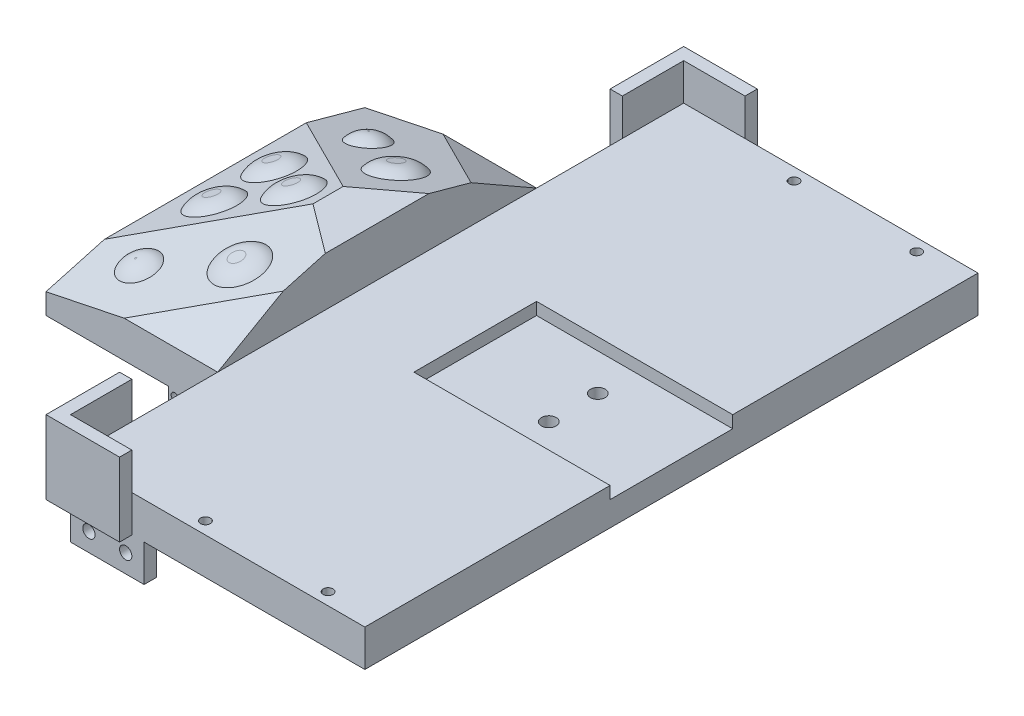
SolidWorks part; units mm, degrees
ref_plane "Ebene vorne" through (0, 0, 0) normal (0, 0, 1) x (1, 0, 0)
ref_plane "Ebene oben" through (0, 0, 0) normal (0, 1, 0) x (1, 0, 0)
ref_plane "Ebene rechts" through (0, 0, 0) normal (1, 0, 0) x (0, 0, -1)
sketch "Skizze1" plane through (0, 0, 0) normal (0, 1, 0) x (1, 0, 0)
  line L5 (-175, -125) -> (175, 125) construction
  line L6 (-175, 125) -> (175, -125) construction
  line L11 (-105, 125) -> (145, 125)
  line L12 (-105, -125) -> (-105, -65)
  line L13 (-105, 125) -> (-105, 65)
  line L14 (-105, -65) -> (-175, -65)
  line L15 (-105, 65) -> (-175, 65)
  line L17 (-105, -125) -> (145, -125)
  line L19 (185, 20) -> (145, 125)
  line L21 (175, 0) -> (175, 20)
  line L22 (175, 20) -> (185, 20)
  line L23 (185, 0) -> (185, 20)
  line L25 (185, 0) -> (185, -20)
  line L26 (185, -20) -> (175, -20)
  line L27 (175, 0) -> (175, -20)
  line L28 (185, -20) -> (145, -125)
  line L29 (-175, 65) -> (-175, -65)
  point P0 (0, 0)
  dimension "D1" = 350
  dimension "D2" = 250
  dimension "D3" = 60
  dimension "D4" = 250
  dimension "D5" = 40
  dimension "D6" = 130
  dimension "D7" = 70
  dimension "D8" = 20
  dimension "D9" = 10
extrude "Aufsatz-Linear austragen1" add sketch "Skizze1" along normal blind 15 contours L15 L29 L14 L12 L17 L28 L26 L27 L21 L22 L19 L11 L13 | L21 L27 L26 L25 L23 L22 region at (10.8182, 0, 0) region at (180, 0, 0)
sketch "Skizze2" plane through (0, 15, 0) normal (0, 1, 0) x (1, 0, 0)
  line L0 (-175, 65) -> (-175, -65) construction
  line L9 (-175, 62) -> (-110, 62)
  line L10 (-175, 62) -> (-175, 42)
  line L11 (-175, 42) -> (-110, 42)
  line L12 (-110, 62) -> (-110, 42)
  line L13 (-105, 65) -> (-175, 65) construction
  line L14 (-175, -42) -> (-110, -42)
  line L15 (-175, -42) -> (-175, -62)
  line L16 (-175, -62) -> (-110, -62)
  line L17 (-110, -42) -> (-110, -62)
  line L18 (-105, -65) -> (-175, -65) construction
  line L19 (-105, 125) -> (145, 125) construction
  line L24 (-125, -62) -> (-120, -62)
  line L25 (-125, -62) -> (-125, -65)
  line L26 (-125, -65) -> (-120, -65)
  line L27 (-120, -62) -> (-120, -65)
  line L28 (-125, -42) -> (-120, -42)
  line L29 (-125, -42) -> (-125, -38)
  line L30 (-125, -38) -> (-120, -38)
  line L31 (-120, -42) -> (-120, -38)
  line L32 (-125, 42) -> (-120, 42)
  line L33 (-125, 42) -> (-125, 38)
  line L34 (-125, 38) -> (-120, 38)
  line L35 (-120, 42) -> (-120, 38)
  line L36 (-125, 65) -> (-120, 65)
  line L37 (-125, 65) -> (-125, 62)
  line L38 (-125, 62) -> (-120, 62)
  line L39 (-120, 65) -> (-120, 62)
  line L40 (-105, -125) -> (145, -125)
  line L41 (-105, -125) -> (-105, 125)
  line L42 (-105, 125) -> (145, 125)
  line L43 (145, -125) -> (145, 125)
  line L46 (145, -125) -> (195, -125)
  line L47 (145, -125) -> (145, 125)
  line L48 (145, 125) -> (195, 125)
  line L49 (195, -125) -> (195, 125)
  line M8 (-105, 65) -> (-175, 65)
  dimension "D1" = 65
  dimension "D2" = 65
  dimension "D3" = 20
  dimension "D4" = 20
  dimension "D5" = 3
  dimension "D6" = 3
  dimension "D7" = 5
  dimension "D8" = 50
  dimension "D9" = 5
  dimension "D10" = 50
  dimension "D11" = 5
  dimension "D12" = 50
  dimension "D13" = 5
  dimension "D14" = 50
  dimension "D15" = 4
  dimension "D16" = 4
  dimension "D17" = 250
  dimension "D18" = 50
extrude "Aufsatz-Linear austragen2" add sketch "Skizze2" against normal blind 37 contours L14 L31 L30 L29 | L35 L11 L33 L34 | L39 L37 L9 M8 | L26 L27 L24 L25 region at (-122.5, 15, -63.5) region at (-122.5, 15, -40) region at (-122.5, 15, 40)
sketch "Skizze3" plane through (0, 15, 0) normal (0, 1, 0) x (1, 0, 0)
  line L0 (-105, 125) -> (145, 125) construction
  line L1 (-105, -125) -> (145, -125)
  line L2 (-105, -125) -> (-105, 125)
  line L3 (-105, 125) -> (145, 125)
  line L4 (145, -125) -> (145, 125)
  line L6 (145, -125) -> (195, -125)
  line L7 (145, -125) -> (145, 125)
  line L8 (145, 125) -> (195, 125)
  line L9 (195, -125) -> (195, 125)
  line M6 (145, -125) -> (185, -20)
  line M7 (185, -20) -> (185, 20)
  line M8 (185, 20) -> (145, 125)
  dimension "D1" = 250
  dimension "D2" = 50
extrude "Aufsatz-Linear austragen3" add sketch "Skizze3" against normal blind 15 contours L6 L9 L8 M8 M7 M6 region at (167.3825, 15, 73.4076)
sketch "Skizze4" plane through (0, 15, 0) normal (0, 1, 0) x (1, 0, 0)
  line L9 (195, -125) -> (200, -125)
  line L10 (195, -125) -> (195, 125)
  line L11 (195, 125) -> (200, 125)
  line L12 (200, -125) -> (200, 125)
  dimension "D3" = 250
  dimension "D4" = 5
extrude "Aufsatz-Linear austragen4" add sketch "Skizze4" against normal blind 15
sketch "Skizze5" plane through (0, 15, 0) normal (0, 1, 0) x (1, 0, 0)
  line L1 (-105, 125) -> (-75, 125)
  line L2 (-105, 125) -> (-105, 120)
  line L3 (-105, 120) -> (-75, 120)
  line L4 (-75, 125) -> (-75, 120)
  line L5 (-105, -125) -> (-75, -125)
  line L6 (-105, -125) -> (-105, -120)
  line L7 (-105, -120) -> (-75, -120)
  line L8 (-75, -125) -> (-75, -120)
  dimension "D1" = 30
  dimension "D2" = 30
  dimension "D3" = 5
  dimension "D4" = 5
extrude "Aufsatz-Linear austragen5" add sketch "Skizze5" against normal blind 30
sketch "Skizze6" plane through (0, 15, 0) normal (0, 1, 0) x (1, 0, 0)
  line L0 (-105, -125) -> (200, -125) construction
  line L1 (-110, -130) -> (-70.4119, -130)
  line L2 (-110, -130) -> (-110, -86.8064)
  line L3 (-110, -86.8064) -> (-70.4119, -86.8064)
  line L4 (-70.4119, -130) -> (-70.4119, -86.8064)
  line L5 (-110, 130) -> (-61.5934, 130)
  line L6 (-110, 130) -> (-110, 88.8696)
  line L7 (-110, 88.8696) -> (-61.5934, 88.8696)
  line L8 (-61.5934, 130) -> (-61.5934, 88.8696)
  line L9 (-105, -125) -> (-105, -65) construction
  line L10 (-105, 125) -> (-105, 65) construction
  line L11 (-105, 125) -> (200, 125) construction
  line L12 (-68.8744, -125) -> (-105, -125)
  line L13 (-105, -125) -> (-105, -86.8064)
  line L14 (-105, 84.0053) -> (-105, 125)
  line L15 (-105, 125) -> (-61.5934, 125)
  line M6 (-105, -65) -> (-105, -125)
  line M7 (-105, -125) -> (200, -125)
  line M9 (200, 125) -> (-105, 125)
  line M10 (-105, 125) -> (-105, 65)
  dimension "D1" = 5
  dimension "D2" = 5
  dimension "D3" = 5
  dimension "D4" = 5
extrude "Aufsatz-Linear austragen6" add sketch "Skizze6" along normal blind 15 separate body contours L8 L5 L6 L7 M10 M9 | L1 L4 L3 L2 M7 M6 region at (-109.4141, 15, 108.4032) region at (-85.7967, 15, -129.3648)
sketch "Skizze7" plane through (0, 0, 0) normal (0, -1, 0) x (1, 0, 0)
  line L7 (-110, -130) -> (-110, -88.8696)
  line L8 (-110, -88.8696) -> (-105, -88.8696)
  line L9 (-105, -130) -> (-105, -88.8696)
  line L10 (-110, 130) -> (-105, 130)
  line L11 (-110, 130) -> (-110, 86.8064)
  line L12 (-110, 86.8064) -> (-105, 86.8064)
  line L13 (-105, 130) -> (-105, 86.8064)
  line L14 (-110, 130) -> (-70.4119, 130)
  line L15 (-110, 130) -> (-110, 125)
  line L16 (-110, 125) -> (-70.4119, 125)
  line L17 (-70.4119, 130) -> (-70.4119, 125)
  line L18 (-110, -130) -> (-61.5934, -130)
  line L19 (-110, -130) -> (-110, -125)
  line L20 (-110, -125) -> (-61.5934, -125)
  line L21 (-61.5934, -130) -> (-61.5934, -125)
  line M7 (-105, 120) -> (-105, 65)
  line M19 (-105, -65) -> (-105, -120)
  line M22 (-75, -125) -> (200, -125)
  line M24 (200, 125) -> (-75, 125)
extrude "Aufsatz-Linear austragen7" add sketch "Skizze7" against normal blind 15 contours L7 L20 L9 L8 M19 | L20 L7 L18 L9 | L18 L21 L20 L9 M22 | L16 L11 L12 L13 M7 | L11 L16 L13 L10 | L17 L14 L13 L16 M24 region at (-107.5, 0, -127.5) region at (-107.5, 0, -106.9348) region at (-83.2967, 0, -127.5) region at (-107.5, 0, 127.5) region at (-87.7059, 0, 127.5) region at (-107.5, 0, 105.9032)
sketch "Skizze8" plane through (0, 15, 0) normal (0, 1, 0) x (1, 0, 0)
  line L0 (-61.5934, 125) -> (200, 125) construction
  line L1 (-105, -125) -> (145, -125)
  line L2 (-105, -125) -> (-105, 125)
  line L3 (-105, 125) -> (145, 125)
  line L4 (145, -125) -> (145, 125)
  line L6 (150, -130) -> (109.2888, -130)
  line L7 (150, -130) -> (150, -94.2536)
  line L8 (150, -94.2536) -> (109.2888, -94.2536)
  line L9 (109.2888, -130) -> (109.2888, -94.2536)
  line L10 (150, 130) -> (118.9946, 130)
  line L11 (150, 130) -> (150, 95.9912)
  line L12 (150, 95.9912) -> (118.9946, 95.9912)
  line L13 (118.9946, 130) -> (118.9946, 95.9912)
  line M9 (-70.4119, -125) -> (200, -125)
  line M11 (200, 125) -> (-61.5934, 125)
  dimension "D1" = 250
  dimension "D2" = 5
  dimension "D3" = 5
  dimension "D4" = 5
  dimension "D5" = 5
extrude "Aufsatz-Linear austragen8" add sketch "Skizze8" along normal blind 15 and the other way blind 15 contours L7 L8 L4 M9 | L9 L6 L7 L1 M9 | L12 L11 L4 M11 | L10 L13 L11 M11 region at (129.6444, 15, 127.5) region at (147.5, 15, 109.6268) region at (134.4973, 15, -127.5) region at (147.5, 15, -110.4956)
sketch "Skizze9" plane through (0, 15, 0) normal (0, 1, 0) x (1, 0, 0)
  line L1 (150, -125) -> (200, -125)
  line L2 (150, -125) -> (150, 125)
  line L3 (150, 125) -> (200, 125)
  line L4 (200, -125) -> (200, 125)
  line L5 (150, 9) -> (196, 9)
  line L6 (150, 9) -> (150, 120)
  line L7 (150, 120) -> (196, 120)
  line L8 (196, 9) -> (196, 120)
  line L10 (200, 105) -> (196, 105)
  line L12 (155, 4) -> (145, 4)
  line L13 (155, 4) -> (155, 14)
  line L14 (155, 14) -> (145, 14)
  line L15 (145, 4) -> (145, 14)
  line L17 (190, 14) -> (200, 14)
  line L18 (190, 14) -> (190, 4)
  line L19 (190, 4) -> (200, 4)
  line L20 (200, 14) -> (200, 4)
  line M10 (150, 125) -> (150, 95.9912)
  line M31 (200, 125) -> (150, 125)
  dimension "D1" = 46
  dimension "D2" = 111
  dimension "D3" = 5
  dimension "D4" = 20
  dimension "D5" = 10
  dimension "D6" = 10
  dimension "D7" = 5
  dimension "D8" = 5
  dimension "D9" = 10
  dimension "D10" = 10
  dimension "D11" = 5
extrude "Aufsatz-Linear austragen10" add sketch "Skizze9" along normal blind 15 contours L15 L12 L2 L14 | L12 L13 L5 L2 | L18 L19 L4 L17 L8 L5 | L10 L4 L7 L8 M31 M10 region at (147.5, 15, -9) region at (152.5, 15, -6.5) region at (195.8571, 15, -7.9286) region at (179.4516, 15, -120.5645)
sketch "Skizze10" plane through (118.9946, 0, 0) normal (-1, 0, 0) x (0, 0, 1)
  line L1 (-125, 30) -> (-130, 30)
  line L2 (-125, 30) -> (-125, 0)
  line L3 (-125, 0) -> (-130, 0)
  line L4 (-130, 30) -> (-130, 0)
extrude "Schnitt-Linear austragen1" cut sketch "Skizze10" against normal blind 1.01
sketch "Skizze12" plane through (0, 15, 0) normal (0, 1, 0) x (1, 0, 0)
  line L0 (-105, 125) -> (-105, 88.8696) construction
  line L1 (-110, 130) -> (-105, 130)
  line L2 (-110, 130) -> (-110, 100)
  line L3 (-110, 100) -> (-105, 100)
  line L4 (-105, 130) -> (-105, 100)
  line L5 (145, 95.9912) -> (145, 125) construction
  line L6 (-105, -125) -> (-70.4119, -125) construction
  line L7 (-110, -130) -> (-80, -130)
  line L8 (-110, -130) -> (-110, -125)
  line L9 (-110, -125) -> (-80, -125)
  line L10 (-80, -130) -> (-80, -125)
  line L11 (-61.5934, 125) -> (-105, 125) construction
  line L12 (-110, 130) -> (-80, 130)
  line L13 (-110, 130) -> (-110, 125)
  line L14 (-110, 125) -> (-80, 125)
  line L15 (-80, 130) -> (-80, 125)
  line L16 (120.0046, 125) -> (145, 125) construction
  line L17 (150, 130) -> (120, 130)
  line L18 (150, 130) -> (150, 125)
  line L19 (150, 125) -> (120, 125)
  line L20 (120, 130) -> (120, 125)
  line L21 (150, 130) -> (145, 130)
  line L22 (150, 130) -> (150, 100)
  line L23 (150, 100) -> (145, 100)
  line L24 (145, 130) -> (145, 100)
  line L25 (145, -125) -> (145, -94.2536) construction
  line L26 (150, -130) -> (145, -130)
  line L27 (150, -130) -> (150, -100)
  line L28 (150, -100) -> (145, -100)
  line L29 (145, -130) -> (145, -100)
  line L30 (109.2888, -125) -> (145, -125) construction
  line L31 (150, -130) -> (120, -130)
  line L32 (150, -130) -> (150, -125)
  line L33 (150, -125) -> (120, -125)
  line L34 (120, -130) -> (120, -125)
  line L36 (-105, -86.8064) -> (-105, -125) construction
  line L37 (-110, -130) -> (-105, -130)
  line L38 (-110, -130) -> (-110, -100)
  line L39 (-110, -100) -> (-105, -100)
  line L40 (-105, -130) -> (-105, -100)
  line L42 (-80, -125) -> (-70.4119, -125)
  line L43 (-80, -125) -> (-80, -130)
  line L44 (-80, -130) -> (-70.4119, -130)
  line L45 (-70.4119, -125) -> (-70.4119, -130)
  line L46 (-105, -100) -> (-110, -100)
  line L47 (-105, -100) -> (-105, -86.8064)
  line L48 (-105, -86.8064) -> (-110, -86.8064)
  line L49 (-110, -100) -> (-110, -86.8064)
  line L50 (-105, 100) -> (-110, 100)
  line L51 (-105, 100) -> (-105, 88.8696)
  line L52 (-105, 88.8696) -> (-110, 88.8696)
  line L53 (-110, 100) -> (-110, 88.8696)
  line L54 (-80, 125) -> (-61.5934, 125)
  line L55 (-80, 125) -> (-80, 130)
  line L56 (-80, 130) -> (-61.5934, 130)
  line L57 (-61.5934, 125) -> (-61.5934, 130)
  line L58 (150, 100) -> (145, 100)
  line L59 (150, 100) -> (150, 95.9912)
  line L60 (150, 95.9912) -> (145, 95.9912)
  line L61 (145, 100) -> (145, 95.9912)
  line L62 (150, -100) -> (145, -100)
  line L63 (150, -100) -> (150, -94.2536)
  line L64 (150, -94.2536) -> (145, -94.2536)
  line L65 (145, -100) -> (145, -94.2536)
  line L66 (120, -125) -> (109.2888, -125)
  line L67 (120, -125) -> (120, -130)
  line L68 (120, -130) -> (109.2888, -130)
  line L69 (109.2888, -125) -> (109.2888, -130)
  line M12 (150, 120) -> (150, 95.9912)
  line M13 (150, 95.9912) -> (145, 95.9912)
  line M14 (145, 95.9912) -> (145, 125)
  line M17 (-61.5934, 125) -> (-105, 125)
  line M18 (-105, 125) -> (-105, 88.8696)
  line M24 (-105, -86.8064) -> (-105, -125)
  line M25 (-105, -125) -> (-70.4119, -125)
  line M27 (109.2888, -125) -> (145, -125)
  line M28 (145, -125) -> (145, -94.2536)
  line M29 (145, -94.2536) -> (150, -94.2536)
  line M30 (150, -94.2536) -> (150, -125)
  dimension "D1" = 30
  dimension "D2" = 30
  dimension "D3" = 30
  dimension "D4" = 30
  dimension "D5" = 30
  dimension "D6" = 30
  dimension "D7" = 30
  dimension "D8" = 30
extrude "Schnitt-Linear austragen2" cut sketch "Skizze12" along normal blind 15 contours L69 L68 L34 M27 | L28 M30 M29 M28 | L23 M12 M14 M13 | L57 L56 L15 M17 | L3 L53 L52 M18 | L45 L10 L44 M25 | L49 L39 L48 M24 region at (-70.7967, 15, -127.5) region at (-107.5, 15, -94.4348) region at (-75.2059, 15, 127.5) region at (-107.5, 15, 93.4032) region at (147.5, 15, -97.9956) region at (114.6444, 15, 127.5) region at (147.5, 15, 97.1268)
sketch "Skizze13" plane through (0, 15, 0) normal (0, 1, 0) x (1, 0, 0)
  line L1 (109.2888, -130) -> (120, -130)
  line L2 (109.2888, -130) -> (109.2888, -125)
  line L3 (109.2888, -125) -> (120, -125)
  line L4 (120, -130) -> (120, -125)
  line L5 (-70.4119, -130) -> (-80, -130)
  line L6 (-70.4119, -130) -> (-70.4119, -125)
  line L7 (-70.4119, -125) -> (-80, -125)
  line L8 (-80, -130) -> (-80, -125)
  line L9 (-110, -86.8064) -> (-105, -86.8064)
  line L10 (-110, -86.8064) -> (-110, -100)
  line L11 (-110, -100) -> (-105, -100)
  line L12 (-105, -86.8064) -> (-105, -100)
  line L13 (-110, 88.8696) -> (-105, 88.8696)
  line L14 (-110, 88.8696) -> (-110, 100)
  line L15 (-110, 100) -> (-105, 100)
  line L16 (-105, 88.8696) -> (-105, 100)
  line L17 (-61.5934, 130) -> (-80, 130)
  line L18 (-61.5934, 130) -> (-61.5934, 125)
  line L19 (-61.5934, 125) -> (-80, 125)
  line L20 (-80, 130) -> (-80, 125)
extrude "Schnitt-Linear austragen3" cut sketch "Skizze13" against normal blind 15
sketch "Skizze14" plane through (0, 15, 0) normal (0, 1, 0) x (1, 0, 0)
  line L1 (-175, -65) -> (-105, -65)
  line L2 (-175, -65) -> (-175, 65)
  line L3 (-175, 65) -> (-105, 65)
  line L4 (-105, -65) -> (-105, 65)
  line L5 (-175, -25) -> (-105, -25)
  line L6 (-175, -25) -> (-175, 25)
  line L7 (-175, 25) -> (-105, 25)
  line L8 (-105, -25) -> (-105, 25)
  line L9 (-105, -25) -> (-125, -25)
  line L10 (-105, -25) -> (-105, 25)
  line L11 (-105, 25) -> (-125, 25)
  line L12 (-125, -25) -> (-125, 25)
  line M34 (-105, 65) -> (-175, 65)
  line M35 (-175, 65) -> (-175, -65)
  line M36 (-175, -65) -> (-105, -65)
  dimension "D1" = 50
  dimension "D2" = 40
  dimension "D3" = 20
  dimension "D4" = 50
extrude "Aufsatz-Linear austragen11" add sketch "Skizze14" along normal blind 20 contours L5 L2 L4 M36 | L5 L12 L7 L2 | L12 L5 L4 L7 | L7 L4 M35 M34 region at (-140, 15, 45) region at (-150, 15, 0) region at (-115, 15, 0) region at (-140, 15, -45)
chamfer "Fase2" distance 20 distance2 50 1 edges at (-175, 35, 0) first distance on face at (-175, 17.5, 0)
chamfer "Fase3" distance 20 distance2 35 2 edges at (-115, 35, -65) (-115, 35, 65) first distance on face at (-128, 5.6, -65) first distance on face at (-128, 5.6, 65)
chamfer "Fase4" distance 20 distance2 20 2 edges at (-150, 25, 47.5) (-150, 25, -47.5)
sketch "Skizze15" plane through (-11.552, 55.8863, -15.4322) normal (-0.1954, 0.9453, -0.261) x (0.9807, 0.1884, -0.052)
  line L0 (-95.2849, 28.8709) -> (-95.2849, 11.0403) construction
  line L1 (-115.678, -3.3909) -> (-166.6609, 35.67) construction
  circle A0 centre (-117.2849, 20.601) radius 10
  circle A1 centre (-142.8398, 36.3157) radius 7.5
  dimension "D1" = 20
  dimension "D2" = 15
  dimension "D3" = 30
  dimension "D4" = 22
  dimension "D5" = 15
extrude "Aufsatz-Linear austragen12" add sketch "Skizze15" along normal blind 3
fillet "Verrundung1" radius 10 2 edges at (-152.2243, 24.1474, -36.5621) (-127.1621, 33.8091, -20.3337)
sketch "Skizze18" plane through (-11.552, 55.8863, 15.4322) normal (-0.1954, 0.9453, 0.261) x (0.9807, 0.1884, 0.052)
  line L0 (-166.6609, -35.67) -> (-115.678, 3.3909) construction
  line L1 (-95.2849, -11.0403) -> (-95.2849, -28.8709) construction
  circle A0 centre (-117.2849, -25.9789) radius 10
  circle A1 centre (-147.2849, -39.7214) radius 7.5
  dimension "D1" = 20
  dimension "D2" = 15
  dimension "D3" = 30
  dimension "D4" = 15
  dimension "D5" = 22
extrude "Aufsatz-Linear austragen13" add sketch "Skizze18" along normal blind 3
fillet "Verrundung2" radius 10 2 edges at (-156.5838, 18.411, 54.0726) (-127.1621, 27.0541, 44.7961)
sketch "Skizze19" plane through (-29.3103, 73.2759, 0) normal (-0.3714, 0.9285, 0) x (0.9285, 0.3714, 0)
  line L0 (-156.9126, -41.147) -> (-156.9126, 41.147) construction
  line L1 (-103.0609, 6.147) -> (-103.0609, -6.147) construction
  line L3 (-156.9126, -41.147) -> (-103.0609, -6.147) construction
  line L4 (-103.0609, 6.147) -> (-156.9126, 41.147) construction
  circle A0 centre (-118.0609, -0.0632) radius 10
  circle A1 centre (-139.8608, 12.1747) radius 10
  circle A2 centre (-139.9126, -12.2084) radius 10
  dimension "D1" = 15
  dimension "D2" = 15
  dimension "D3" = 17
  dimension "D4" = 17.0518
  dimension "D5" = 25
  dimension "D7" = 15
  dimension "D8" = 25
extrude "Aufsatz-Linear austragen14" add sketch "Skizze19" along normal blind 3
fillet "Verrundung3" radius 10 3 edges at (-149.3261, 28.5007, 0.0632) (-169.6148, 20.3852, 12.2084) (-169.5667, 20.4044, -12.1747)
sketch "Skizze20" plane through (0, 0, -65) normal (0, 0, -1) x (-1, 0, 0)
  line L1 (120, -22) -> (125, -22) construction
  line L2 (120, 0) -> (125, 0)
  line L3 (120, -22) -> (120, 0) construction
  line L4 (125, -22) -> (125, 0) construction
  circle A0 centre (122.5, -19.5) radius 1.5
  circle A1 centre (122.5, -2.5) radius 1.5
  dimension "D1" = 3
  dimension "D2" = 3
  dimension "D3" = 2.5
  dimension "D4" = 2.5
  dimension "D5" = 2.5
  dimension "D6" = 2.5
extrude "Schnitt-Linear austragen4" cut sketch "Skizze20" against normal blind 250 contours A0 | A1 region at (-122.5, -19.5, -65) region at (-122.5, -2.5, -65)
sketch "Skizze21" plane through (0, 15, 0) normal (0, 1, 0) x (1, 0, 0)
  line L0 (200, -125) -> (200, 4) construction
  line L1 (197.5893, -53.9558) -> (147.5893, -53.9558)
  line L2 (197.5893, -53.9558) -> (197.5893, 1.0442)
  line L3 (197.5893, 1.0442) -> (147.5893, 1.0442)
  line L4 (147.5893, -53.9558) -> (147.5893, 1.0442)
  line L9 (150, -100) -> (191, -100)
  line L10 (150, -100) -> (150, -118)
  line L11 (150, -118) -> (191, -118)
  line L12 (191, -100) -> (191, -118)
  line L13 (145, -100) -> (195, -100)
  line L14 (145, -100) -> (145, -93)
  line L15 (145, -93) -> (195, -93)
  line L16 (195, -100) -> (195, -93)
  line L17 (150, -125) -> (200, -125)
  line L18 (150, -125) -> (150, -118)
  line L19 (150, -118) -> (200, -118)
  line L20 (200, -125) -> (200, -118)
  line L22 (195, -93) -> (191, -93)
  line L23 (195, -93) -> (195, -105.2)
  line L24 (195, -105.2) -> (191, -105.2)
  line L25 (191, -93) -> (191, -105.2)
  line L26 (195, -125) -> (191, -125)
  line L27 (195, -125) -> (195, -112.8)
  line L28 (195, -112.8) -> (191, -112.8)
  line L29 (191, -125) -> (191, -112.8)
  line M31 (145, -100) -> (150, -100)
  line M32 (150, -100) -> (150, -125)
  line M33 (150, -125) -> (200, -125)
  dimension "D1" = 55
  dimension "D2" = 50
  dimension "D3" = 41
  dimension "D4" = 18
  dimension "D5" = 7
  dimension "D6" = 4
  dimension "D7" = 12.2
  dimension "D8" = 4
  dimension "D9" = 12.2
extrude "Aufsatz-Linear austragen15" add sketch "Skizze21" along normal blind 10 contours L25 L15 L14 L9 M31 | L15 L25 L13 L16 | L24 L23 L13 L12 | L29 L11 M33 M32 | L29 L17 L27 L19 | L27 L28 L12 L19 region at (168, 15, 96.5) region at (193, 15, 102.6) region at (193, 15, 96.5) region at (170.5, 15, 121.5) region at (193, 15, 115.4) region at (193, 15, 121.5)
sketch "Skizze22" plane through (0, 15, 0) normal (0, 1, 0) x (1, 0, 0)
  line L1 (140.9695, -63.333) -> (190.9695, -63.333)
  line L2 (140.9695, -63.333) -> (140.9695, -8.333)
  line L3 (140.9695, -8.333) -> (190.9695, -8.333)
  line L4 (190.9695, -63.333) -> (190.9695, -8.333)
  circle A0 centre (146.0695, -58.233) radius 1.75
  circle A1 centre (146.0695, -13.433) radius 1.75
  circle A2 centre (185.8695, -58.233) radius 1.75
  circle A3 centre (185.8695, -13.433) radius 1.75
  dimension "D1" = 3.5
  dimension "D2" = 3.5
  dimension "D3" = 3.5
  dimension "D4" = 3.5
  dimension "D5" = 5.1
  dimension "D6" = 5.1
  dimension "D7" = 50
  dimension "D8" = 55
  dimension "D9" = 5.1
  dimension "D10" = 5.1
  dimension "D11" = 5.1
  dimension "D12" = 5.1
  dimension "D13" = 5.1
  dimension "D14" = 5.1
extrude "Schnitt-Linear austragen5" cut sketch "Skizze22" against normal blind 20 contours A0 | A1 | A3 | A2
sketch "Skizze25" plane through (0, 15, 0) normal (0, 1, 0) x (1, 0, 0)
  line L0 (-175, -41.147) -> (-175, 41.147) construction
  line L1 (15, 146.8783) -> (227.9673, 146.8783)
  line L2 (15, 146.8783) -> (15, -156.3563)
  line L3 (15, -156.3563) -> (227.9673, -156.3563)
  line L4 (227.9673, 146.8783) -> (227.9673, -156.3563)
  dimension "D1" = 190
extrude "Schnitt-Linear austragen8" cut sketch "Skizze25" against normal blind 50 and the other way blind 50
sketch "Skizze26" plane through (15, 0, 0) normal (1, 0, 0) x (0, 0, -1)
  line L0 (-125, 15) -> (125, 15) construction
  line L1 (-25, 15) -> (25, 15)
  line L2 (-25, 15) -> (-25, 10)
  line L3 (-25, 10) -> (25, 10)
  line L4 (25, 15) -> (25, 10)
  line L7 (125, 15) -> (125, 0) construction
  dimension "D1" = 5
  dimension "D2" = 50
  dimension "D3" = 100
extrude "Schnitt-Linear austragen9" cut sketch "Skizze26" against normal blind 80
sketch "Skizze27" plane through (0, 15, 0) normal (0, 1, 0) x (1, 0, 0)
  line L1 (15, -25) -> (-65, -25)
  line L2 (15, -25) -> (15, 25)
  line L3 (15, 25) -> (-65, 25)
  line L4 (-65, -25) -> (-65, 25)
sketch "Skizze28" plane through (0, 10, 0) normal (0, 1, 0) x (1, 0, 0)
  line L0 (-65, 25) -> (15, 25) construction
  line L1 (-65, -25) -> (-65, 25) construction
  circle A0 centre (-35, 0) radius 12.5
  dimension "D3" = 25
  dimension "D1" = 25
  dimension "D2" = 30
extrude "Schnitt-Linear austragen10" cut sketch "Skizze28" against normal blind 80
sketch "Skizze29" plane through (0, 0, 0) normal (0, -1, 0) x (-1, 0, 0)
  circle A0 centre (35, 0) radius 23.1296
extrude "Aufsatz-Linear austragen16" add sketch "Skizze29" against normal blind 10
sketch "Skizze32" plane through (0, 15, 0) normal (0, 1, 0) x (1, 0, 0)
  line L0 (15, 125) -> (-105, 125)
  line L16 (15, -25) -> (-65, -25)
  line L17 (-65, -25) -> (-65, 25)
  line L18 (-65, 25) -> (15, 25)
  line L19 (15, 25) -> (15, 125)
  line L20 (15, 125) -> (-80, 125)
  line L21 (-80, 125) -> (-105, 125)
  line L22 (-105, 125) -> (-105, 100)
  line L23 (-105, 100) -> (-105, 65)
  line L24 (-105, 65) -> (-105, -65)
  line L25 (-105, -65) -> (-105, -100)
  line L26 (-105, -100) -> (-105, -125)
  line L27 (-105, -125) -> (-80, -125)
  line L28 (-80, -125) -> (15, -125)
  line L29 (15, -125) -> (15, -25)
  line L34 (15, 125) -> (-80, 125)
  line L35 (-80, 125) -> (-105, 125)
  dimension "D1" = 0
sketch "Skizze33" plane through (-65, 0, 0) normal (1, 0, 0) x (0, 0, -1)
  line L1 (-25, 15) -> (25, 15)
  line L2 (-25, 15) -> (-25, 10)
  line L3 (-25, 10) -> (25, 10)
  line L4 (25, 15) -> (25, 10)
extrude "Aufsatz-Linear austragen17" add sketch "Skizze33" along normal blind 160
sketch "Skizze34" plane through (0, 0, 0) normal (0, -1, 0) x (-1, 0, 0)
  line L1 (65, 25) -> (-95, 25)
  line L2 (65, 25) -> (65, -25)
  line L3 (65, -25) -> (-95, -25)
  line L4 (-95, 25) -> (-95, -25)
extrude "Aufsatz-Linear austragen18" add sketch "Skizze34" along normal blind 15
sketch "Skizze36" plane through (0, 0, 125) normal (0, 0, 1) x (1, 0, 0)
  line L1 (-105, -15) -> (-75, -15) construction
  line L2 (-75, -15) -> (-75, 0) construction
  circle A0 centre (-97.5, -7.5) radius 2.5
  circle A1 centre (-82.5, -7.5) radius 2.5
  dimension "D5" = 5
  dimension "D6" = 5
  dimension "D1" = 7.5
  dimension "D2" = 7.5
  dimension "D3" = 15
  dimension "D4" = 7.5
extrude "Schnitt-Linear austragen12" cut sketch "Skizze36" against normal blind 250
sketch "Skizze37" plane through (0, 15, 0) normal (0, 1, 0) x (1, 0, 0)
  line L1 (15, -25) -> (95, -25)
  line L2 (15, -25) -> (15, 25)
  line L3 (15, 25) -> (95, 25)
  line L4 (95, -25) -> (95, 25)
  circle A0 centre (35, -10) radius 3
  circle A1 centre (35, 10) radius 3
  circle A2 centre (75, -10) radius 3
  circle A3 centre (75, 10) radius 3
  dimension "D1" = 6
  dimension "D2" = 6
  dimension "D3" = 6
  dimension "D4" = 6
  dimension "D7" = 15
  dimension "D5" = 20
  dimension "D6" = 15
  dimension "D8" = 20
  dimension "D9" = 20
  dimension "D10" = 20
  dimension "D11" = 40
  dimension "D12" = 40
extrude "Schnitt-Linear austragen16" cut sketch "Skizze37" against normal blind 78 contours A0 | A1 | A2 | A3
sketch "Skizze38" plane through (0, 15, 0) normal (0, 1, 0) x (1, 0, 0)
  line L0 (15, -125) -> (15, -25) construction
  line L1 (15, 25) -> (15, 125) construction
  line L2 (15, 125) -> (-105, 125) construction
  line L3 (-80, -125) -> (15, -125) construction
  circle A0 centre (-55, -120) radius 2
  circle A1 centre (-5, -120) radius 2
  circle A2 centre (-5, 120) radius 2
  circle A3 centre (-55, 120) radius 2
  dimension "D1" = 4
  dimension "D2" = 4
  dimension "D3" = 4
  dimension "D4" = 4
  dimension "D11" = 5
  dimension "D5" = 20
  dimension "D6" = 50
  dimension "D7" = 20
  dimension "D8" = 50
  dimension "D9" = 5
  dimension "D10" = 5
  dimension "D12" = 5
extrude "Schnitt-Linear austragen17" cut sketch "Skizze38" against normal blind 50 contours A1 | A0 | A3 | A2
sketch "Skizze39" plane through (0, -15, 0) normal (0, -1, 0) x (-1, 0, 0)
  line L1 (-95, -25) -> (65, -25)
  line L2 (-95, -25) -> (-95, 25)
  line L3 (-95, 25) -> (65, 25)
  line L4 (65, -25) -> (65, 25)
  dimension "D1" = 160
  dimension "D2" = 50
extrude "Schnitt-Linear austragen18" cut sketch "Skizze39" against normal blind 15
sketch "Skizze40" plane through (0, 10, 0) normal (0, -1, 0) x (1, 0, 0)
  line L0 (95, 25) -> (95, -25) construction
  line L1 (95, -25) -> (15, -25) construction
  line L3 (-65, 25) -> (95, 25)
  line L4 (-65, 25) -> (-65, -25)
  line L5 (-65, -25) -> (95, -25)
  line L6 (95, 25) -> (95, -25)
  circle A0 centre (35, -10) radius 3
  circle A1 centre (75, -10) radius 3
  dimension "D4" = 6
  dimension "D1" = 40
  dimension "D2" = 20
  dimension "D3" = 15
extrude "Schnitt-Linear austragen19" cut sketch "Skizze40" against normal blind 5
sketch "Skizze41" plane through (0, 10, 0) normal (0, 1, 0) x (1, 0, 0)
  line L0 (15, -25) -> (-65, -25) construction
  line L1 (-65, -25) -> (-65, 25) construction
  circle A0 centre (-25, -10) radius 3
  circle A1 centre (-25, 10) radius 3
  dimension "D4" = 6
  dimension "D5" = 6
  dimension "D1" = 20
  dimension "D2" = 15
  dimension "D3" = 40
extrude "Schnitt-Linear austragen22" cut sketch "Skizze41" against normal blind 10
